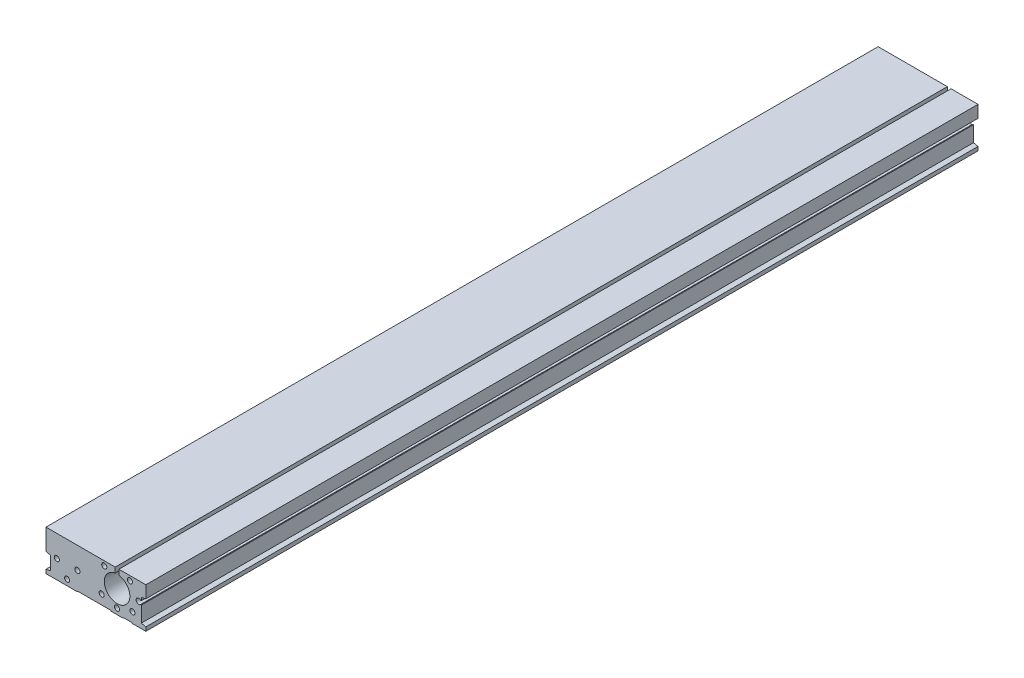
SolidWorks part; units mm, degrees
note: '?' marks a value the reader was unsure of.
material "6061-O (SS)"
ref_plane "Front" through (0, 0, 0) normal (0, 0, 1) x (1, 0, 0)
ref_plane "Top" through (0, 0, 0) normal (0, 1, 0) x (1, 0, 0)
ref_plane "Right" through (0, 0, 0) normal (1, 0, 0) x (0, 0, -1)
sketch "Base_Sketch" plane through (0, 0, 0) normal (0, 0, 1) x (1, 0, 0)
  line L0 (-22.5, 14) -> (-22.5, -17.5) construction
  line L1 (22.5, 14) -> (-55.5, 14)
  line L2 (22.5, 14) -> (22.5, -17.5)
  line L3 (22.5, -17.5) -> (-55.5, -17.5)
  line L4 (-55.5, 14) -> (-55.5, -17.5)
  circle A0 centre (0, 0) radius 10
  dimension "Diameter" = 20
  dimension "HG" = 17.5
  dimension "Height" = 31.5
  dimension "LW" = 78
  dimension "NW/2" = 22.5
  dimension "NW" = 45
extrude "Base" add sketch "Base_Sketch" along normal up to surface (325 mm away) and the other way up to surface (325 mm away)
sketch "Base_Groove_Sketch" plane through (0, 0, 0) normal (0, 0, 1) x (1, 0, 0)
  line L0 (12, -17.5) -> (11.134, -17)
  line L1 (-55.5, -17.5) -> (22.5, -17.5) construction
  line L2 (11.134, -17) -> (5.366, -17)
  line L3 (5.366, -17) -> (4.5, -17.5)
  line L4 (-4.5, -17.5) -> (-5.366, -17)
  line L5 (-5.366, -17) -> (-30.634, -17)
  line L6 (-30.634, -17) -> (-31.5, -17.5)
  line L7 (-31.5, -17.5) -> (-4.5, -17.5)
  line L8 (4.5, -17.5) -> (12, -17.5)
  line L9 (-55.5, 14) -> (-55.5, -17.5) construction
  dimension "Depth" = 0.5
  dimension "Space" = 9
  dimension "Space/2" = 4.5
  dimension "Side_Offset" = 24
  dimension "S_Length" = 7.5
extrude "Base_Groove" cut sketch "Base_Groove_Sketch" against normal through all and the other way through all
sketch "Seal_Groove_Sketch" plane through (0, 0, 0) normal (0, 0, 1) x (1, 0, 0)
  line L1 (1.45, 9.8438) -> (1.45, 16.3) construction
  line L3 (-1.45, 14) -> (-1.45, 9.8943)
  line L4 (1.45, 9.8943) -> (1.45, 14)
  line L5 (22.5, 14) -> (-55.5, 14) construction
  line L6 (0, 0) -> (0, 12.2352) construction
  line L7 (1.45, 14) -> (-1.45, 14)
  line L8 (-1.45, 16.3) -> (-1.45, 9.8438) construction
  circle A1 centre (0, 0) radius 10 construction
  arc A2 (1.45, 9.8943) -> (-1.45, 9.8943) centre (0, 0) ccw
extrude "Seal_Groove" cut sketch "Seal_Groove_Sketch" against normal through all and the other way through all
sketch "Holes_Sketch" plane through (0, 0, 0) normal (0, 0, 1) x (1, 0, 0)
  line L0 (0, 0) -> (0, -16.3992) construction
  line L1 (-55.5, -17.5) -> (-31.5, -17.5) construction
  circle A0 centre (12, -9.5) radius 2
  circle A1 centre (-12, -9.5) radius 2
  circle A2 centre (10, 10.5) radius 2
  circle A3 centre (-10, 10.5) radius 2
  circle A4 centre (0, -13) radius 2
  circle A5 centre (-31, -3) radius 2
  circle A6 centre (-47, -3) radius 2
  circle A7 centre (-39, -13) radius 2
  dimension "Diamter" = 4
  dimension "L_space" = 24
  dimension "L_Middle" = 8
  dimension "LU_Space" = 10
  dimension "L_Lower" = 4.5
  dimension "L_Upper" = 23.5
  dimension "L_S" = 31
  dimension "S_Space" = 16
  dimension "S_Space/2" = 8
  dimension "S_lower" = 4.5
  dimension "SL_SUpper" = 10
extrude "Holes" cut sketch "Holes_Sketch" against normal through all and the other way through all
sketch "Switch_Groove1_Sketch"
  line L0 (0, 0) -> (21.8333, 0) construction
  line L1 (22.5, 1.5) -> (18.4697, 1.5)
  line L3 (22.5, -1.5) -> (18.4697, -1.5)
  line L4 (22.5, 1.5) -> (22.5, -1.5)
  line L5 (22.5, -17.5) -> (22.5, 14) construction
  line L6 (22.5, -17.5) -> (22.5, 14) construction
  arc A0 (18.4697, 1.5) -> (18.4697, -1.5) centre (17, 0) ccw
extrude "Side_Groove2" cut sketch "Side_Groove2_Sketch" against normal through all and the other way through all
sketch "Side_Groove2_Sketch" plane through (0, 0, 0) normal (0, 0, 1) x (1, 0, 0)
  line L0 (22.5, 4.5) -> (19, 3.692)
  line L1 (22.5, -17.5) -> (22.5, -1.5) construction
  line L2 (19, 3.692) -> (19, -13.692)
  line L3 (19, -13.692) -> (22.5, -14.5)
  line L4 (22.5, 4.5) -> (22.5, -14.5)
  line L5 (50, 0) -> (-50, 0) construction
  line L6 (12, -17.5) -> (22.5, -17.5) construction
  dimension "B_Angle" = 13
  dimension "T_Angle" = 13
  dimension "B_Offset" = 3
  dimension "Depth" = 3.5
  dimension "T_Offset" = 22
extrude "Switch_Groove1" cut sketch "Switch_Groove1_Sketch" against normal through all and the other way through all
sketch "Switch_Groove2_Sketch" [suppressed] plane through (0, 0, 0) normal (0, 0, 1) x (1, 0, 0)
  line L0 (0, 0) -> (16.7245, 0) construction
  line L1 (26.5, 2.525) -> (21.6608, 2.525)
  line L3 (21.3, -3.15) -> (21.6608, -2.525)
  line L4 (21.3, 3.15) -> (17.6, 3.15)
  line L5 (17.6, 3.15) -> (17.6, -3.15)
  line L6 (21.3, -3.15) -> (17.6, -3.15)
  line L7 (26.5, 2.525) -> (26.5, -2.525)
  line L8 (26.5, -2.525) -> (21.6608, -2.525)
  line L9 (26.5, -21) -> (26.5, 16.5) construction
  line L10 (26.5, -21) -> (26.5, 16.5) construction
  line L11 (21.3, 3.15) -> (21.6608, 2.525)
  point P11 (17.6, 0)
  dimension "B_width" = 6.3
  dimension "Depth" = 8.9
  dimension "S_width" = 5.05
  dimension "Angle" = 120
  dimension "Switch_Depth" = 3.7
extrude "Switch_Groove2" [suppressed] cut sketch "Switch_Groove2_Sketch" against normal through all and the other way through all
sketch "Side_Groove1_Sketch" plane through (0, 0, 0) normal (0, 0, 1) x (1, 0, 0)
  line L0 (-55.5, -14.5) -> (-52, -13.692)
  line L1 (-52, -13.692) -> (-52, -3.308)
  line L2 (-52, -3.308) -> (-55.5, -2.5)
  line L3 (-55.5, 14) -> (-55.5, -17.5) construction
  line L4 (-55.5, -2.5) -> (-55.5, -14.5)
  line L5 (-55.5, 14) -> (-55.5, -17.5) construction
  line L6 (50, 0) -> (-50, 0) construction
  line L7 (-55.5, -17.5) -> (-31.5, -17.5) construction
  line L8 (-55.5, -17.5) -> (-31.5, -17.5) construction
  dimension "B_Angle" = 13
  dimension "T_Angle" = 13
  dimension "Depth" = 3.5
  dimension "B_Offset" = 3
  dimension "T_Offset" = 15
extrude "Side_Groove1" cut sketch "Side_Groove1_Sketch" against normal through all and the other way through all
ref_axis "Axis1" through (17, 0, -50) along (0, 0, 1)?
ref_plane "SwitchPlaneA" through (0, 0, 304.8) normal (0, 0, 1) x (1, 0, 0)
ref_plane "SwitchPlaneB" through (0, 0, -195.1) normal (0, 0, -1) x (-1, 0, 0)
